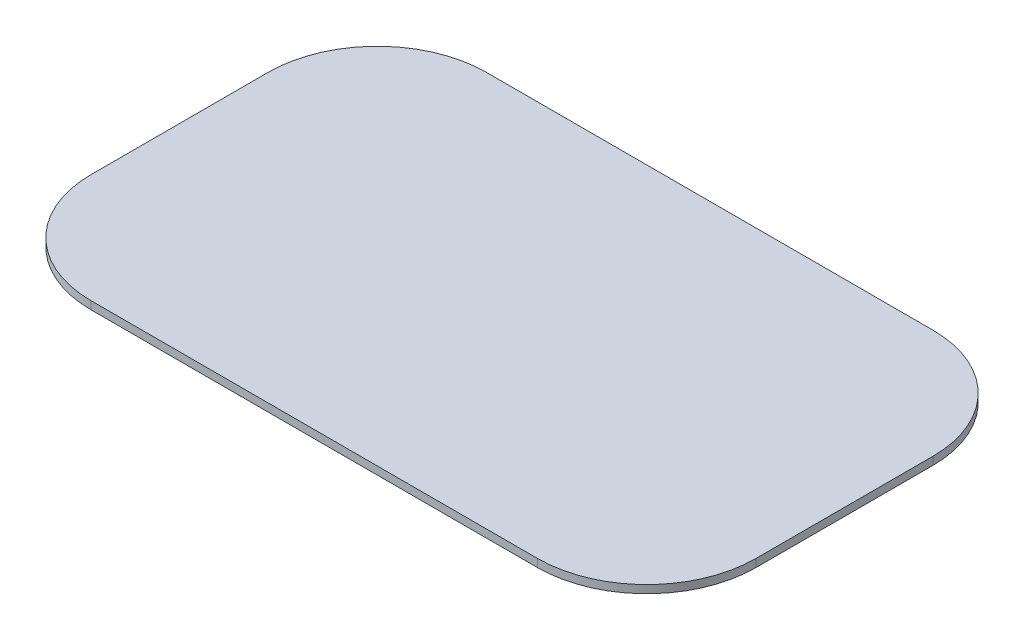
SolidWorks part; units mm, degrees
ref_plane "Front Plane" through (0, 0, 0) normal (0, 0, 1) x (1, 0, 0)
ref_plane "Top Plane" through (0, 0, 0) normal (0, 1, 0) x (1, 0, 0)
ref_plane "Right Plane" through (0, 0, 0) normal (1, 0, 0) x (0, 0, -1)
sketch "Sketch1" plane through (0, 0, 0) normal (0, 1, 0) x (1, 0, 0)
  line L1 (-9.9666, 27.987) -> (215.0634, 27.987)
  line L2 (-64.9666, -27.013) -> (-64.9666, -116.273)
  line L3 (-9.9666, -171.273) -> (215.0634, -171.273)
  line L4 (270.0634, -27.013) -> (270.0634, -116.273)
  arc A0 (-64.9666, -116.273) -> (-9.9666, -171.273) centre (-9.9666, -116.273) ccw
  arc A1 (215.0634, -171.273) -> (270.0634, -116.273) centre (215.0634, -116.273) ccw
  arc A2 (215.0634, 27.987) -> (270.0634, -27.013) centre (215.0634, -27.013) cw
  arc A3 (-9.9666, 27.987) -> (-64.9666, -27.013) centre (-9.9666, -27.013) ccw
  dimension "D3" = 55
extrude "Boss-Extrude1" add sketch "Sketch1" along normal blind 4
